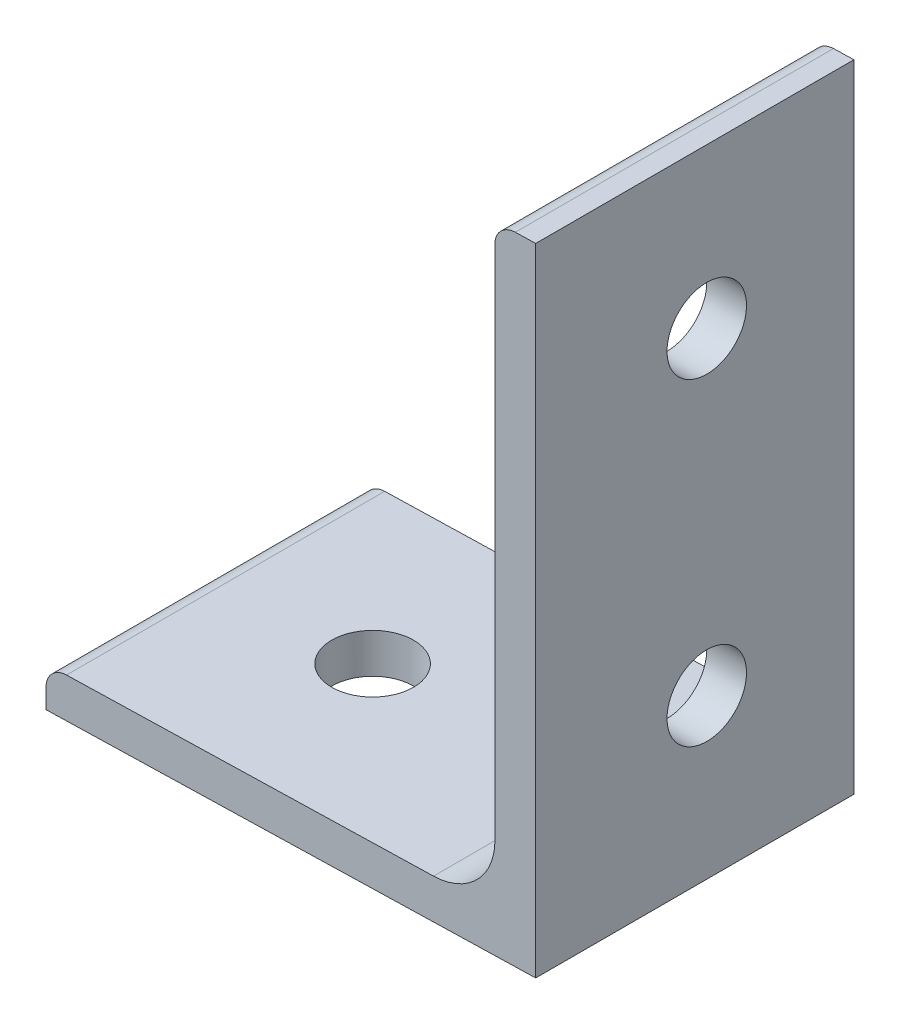
SolidWorks part; units mm, degrees
ref_plane "Front Plane" through (0, 0, 0) normal (0, 0, 1) x (1, 0, 0)
ref_plane "Top Plane" through (0, 0, 0) normal (0, 1, 0) x (1, 0, 0)
ref_plane "Right Plane" through (0, 0, 0) normal (1, 0, 0) x (0, 0, -1)
sketch "Sketch0" plane through (0, 0, 0) normal (0, 0, 1) x (1, 0, 0)
  line L0 (-19.05, -25.4) -> (19.05, -25.4)
  line L1 (19.05, -25.4) -> (19.05, 25.4)
  line L2 (19.05, 0) -> (0, 0) construction
  line L3 (0, 0) -> (0, -25.4) construction
  line L4 (15.875, -17.4498) -> (15.875, 25.4) construction
  line L5 (11.0998, -22.225) -> (-19.05, -22.225) construction
  arc A0 (15.875, -17.4498) -> (11.0998, -22.225) centre (11.0998, -17.4498) cw
  point P3 (14.4764, -20.8264)
  dimension "Inside Corner Radius" = 4.7752
  dimension "Outside Height" = 50.8
  dimension "Inside Height" = 47.625
  dimension "Inside Width" = 34.925
  dimension "Wall Thickness" = 3.175
  dimension "D1" = 3.175
  dimension "Outside Width" = 38.1
sketch "Sketch1" plane through (0, 0, 0) normal (1, 0, 0) x (0, 0, -1)
  line L0 (15.875, 0) -> (-15.875, 0)
  point P4 (0, 0)
  dimension "Length" = 31.75
sketch "Sketch2" plane through (0, 0, 0) normal (0, 0, 1) x (1, 0, 0)
  line L0 (-19.05, -25.4) -> (19.05, -25.4)
  line L1 (19.05, -25.4) -> (19.05, 25.4)
  line L2 (19.05, 25.4) -> (15.875, 25.4) construction
  line L3 (15.875, 23.8125) -> (15.875, -17.4498)
  line L4 (11.0998, -22.225) -> (-17.4625, -22.225)
  line L5 (-19.05, -25.4) -> (-19.05, -22.225) construction
  line L6 (17.4625, 25.4) -> (19.05, 25.4)
  line L7 (-19.05, -23.8125) -> (-19.05, -25.4)
  line L8 (19.05, 0) -> (0, 0) construction
  line L9 (0, 0) -> (0, -25.4) construction
  arc A0 (15.875, 23.8125) -> (17.4625, 25.4) centre (17.4625, 23.8125) cw
  arc A1 (-19.05, -23.8125) -> (-17.4625, -22.225) centre (-17.4625, -23.8125) cw
  arc A2 (15.875, -17.4498) -> (11.0998, -22.225) centre (11.0998, -17.4498) cw
  dimension "Inside Radius" = 4.7752
  dimension "Height" = 50.8
  dimension "Width" = 38.1
  dimension "Thickness" = 3.175
extrude "Boss-Extrude1" add sketch "Sketch2" along normal mid plane 31.75
sketch "Break Locations" plane through (0, 0, 0) normal (1, 0, 0) x (0, 0, -1)
  line L0 (35.941, 0) -> (-35.941, 0)
  line L1 (-15.875, -25.4) -> (-15.875, 25.4) construction
  line L2 (15.875, -25.4) -> (15.875, 25.4) construction
  point P0 (27.305, 0)
  point P1 (-27.305, 0)
  point P10 (0, 0)
  point P11 (-35.941, 0)
  point P13 (35.941, 0)
  dimension "D1" = 43.18
  dimension "D2" = 43.18
  dimension "D3" = 51.816
sketch "Sketch3" plane through (0, -25.4, 0) normal (0, -1, 0) x (1, 0, 0)
  line L0 (-19.05, -13.9268) -> (19.05, -14.9245)
  line L1 (19.05, 15.875) -> (19.05, -15.875) construction
  line L2 (19.05, -14.9245) -> (15.875, -14.8414) construction
  line L4 (-19.05, 11.4819) -> (19.05, 10.4842)
  line L5 (19.05, 10.4842) -> (19.05, -14.9245)
  line L6 (-19.05, -13.9268) -> (-19.05, 11.4819)
sketch "Sketch4" plane through (19.05, 0, 0) normal (1, 0, 0) x (0, 0, -1)
  line L0 (15.875, -25.4) -> (3.175, -25.4) construction
  line L1 (-15.875, -25.4) -> (15.875, -25.4) construction
  line L2 (3.175, -25.4) -> (3.175, -12.7) construction
  line L3 (3.175, -12.7) -> (3.175, 12.7) construction
  circle A0 centre (3.175, 12.7) radius 3.175
  circle A1 centre (3.175, -12.7) radius 3.175
  dimension "D1" = 12.7
  dimension "D2" = 12.7
  dimension "D3" = 25.4
extrude "Cut-Extrude1" cut sketch "Sketch4" against normal through all
extrude "Cut-Extrude2" cut sketch "Sketch3" against normal through all flip side to cut
hole_wizard "1/4 Clearance Hole1" positions "Sketch7" profile "Sketch8" hole size "1/4" standard "ANSI Inch" end condition through all
sketch "Sketch7" plane through (0, -25.4, 0) normal (0, -1, 0) x (-1, 0, 0)
  point P0 (6.0219, 1.5636)
sketch "Sketch8" plane through (-6.0219, -25.4, -1.5636) normal (1, 0, 0) x (0, 0, -1)
  line L0 (0, 0) -> (0, 50.8)
  line L1 (0, 50.8) -> (3.2639, 50.8)
  line L2 (3.2639, 50.8) -> (3.2639, 0)
  line L5 (3.2639, 0) -> (0, 0)
  line L11 (0, -6.35) -> (0, 107.95) construction
  dimension "Thru Hole Dia." = 6.5278
  dimension "Thru Hole Depth" = 50.8
sketch "Sketch9" plane through (15.875, 0, 0) normal (-1, 0, 0) x (0, 0, 1)
  circle A0 centre (-3.175, -12.7) radius 6.35
extrude "Cut-Extrude3" cut sketch "Sketch9" along normal blind 2.54
equation "\"D1@Break Locations\" = .85 * \"Height@Sketch2\""
equation "\"D2@Break Locations\"=\"D1@Break Locations\""
equation "\"Thickness@Sketch2\"=\"wall thickness@sketch0\""
equation "\"Height@Sketch2\"=\"outside height@sketch0\""
equation "\"Width@Sketch2\"=\"outside width@sketch0\""
equation "\"Inside Radius@Sketch2\"=\"inside corner radius@sketch0\""
equation "\"Length@Boss-Extrude1\"=\"length@sketch1\""
equation "\"D3@Break Locations\"=\"D2@Break Locations\"*1.2"
equation "\"D1@Sketch0\"=\"Wall Thickness@Sketch0\""
